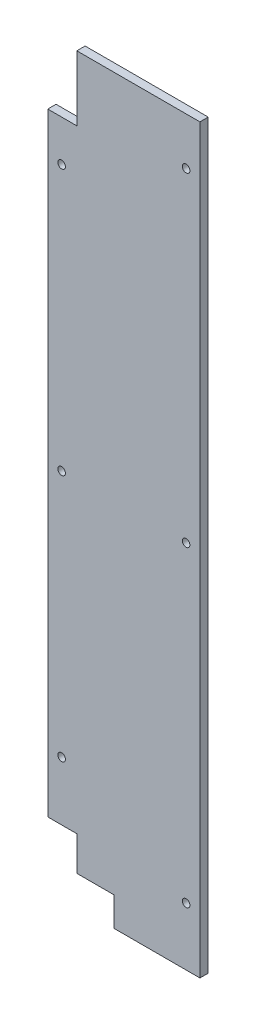
SolidWorks part; units mm, degrees
ref_plane "Front Plane" through (0, 0, 0) normal (0, 0, 1) x (1, 0, 0)
ref_plane "Top Plane" through (0, 0, 0) normal (0, 1, 0) x (1, 0, 0)
ref_plane "Right Plane" through (0, 0, 0) normal (1, 0, 0) x (0, 0, -1)
sketch "Sketch1" plane through (0, 0, 0) normal (0, 0, 1) x (1, 0, 0)
  line L0 (-82.419, -326.8557) -> (-82.419, -305.8557)
  line L1 (-109.419, 209.1443) -> (-20.419, 209.1443)
  line L2 (-130.419, 162.1753) -> (-130.419, -281.0269)
  line L3 (-82.419, -326.8557) -> (-20.419, -326.8557)
  line L4 (-20.419, 209.1443) -> (-20.419, -326.8557)
  line L5 (-82.419, -305.8557) -> (-109.419, -305.8557)
  line L7 (-109.419, 162.1753) -> (-109.419, 209.1443)
  line L8 (-130.419, -281.0269) -> (-109.419, -281.0269)
  line L9 (-109.419, -281.0269) -> (-109.419, -305.8557)
  line L10 (-130.419, 162.1753) -> (-109.419, 162.1753)
  dimension "D1" = 536
  dimension "D2" = 110
  dimension "D4" = 21
  dimension "D5" = 21
  dimension "D6" = 21
  dimension "D7" = 48
extrude "Boss-Extrude1" add sketch "Sketch1" along normal blind 6 contours L1 L4 L3 L0 L5 L9 L8 L2 L10 L7
sketch "Sketch2" plane through (0, 0, 6) normal (0, 0, 1) x (1, 0, 0)
  line L0 (-130.419, 162.1753) -> (-130.419, -281.0269) construction
  line L1 (-20.419, 209.1443) -> (-20.419, -326.8557) construction
  circle A0 centre (-120.419, -59.4258) radius 2.75
  circle A1 centre (-30.419, -59.4258) radius 2.75
  circle A2 centre (-30.419, 174.9442) radius 2.75
  circle A3 centre (-30.419, -284.9376) radius 2.75
  circle A4 centre (-120.419, -238.5628) radius 2.75
  circle A5 centre (-120.419, 132.4555) radius 2.75
  dimension "D1" = 5.5
  dimension "D2" = 10
  dimension "D3" = 10
extrude "Cut-Extrude1" cut sketch "Sketch2" against normal blind 10
